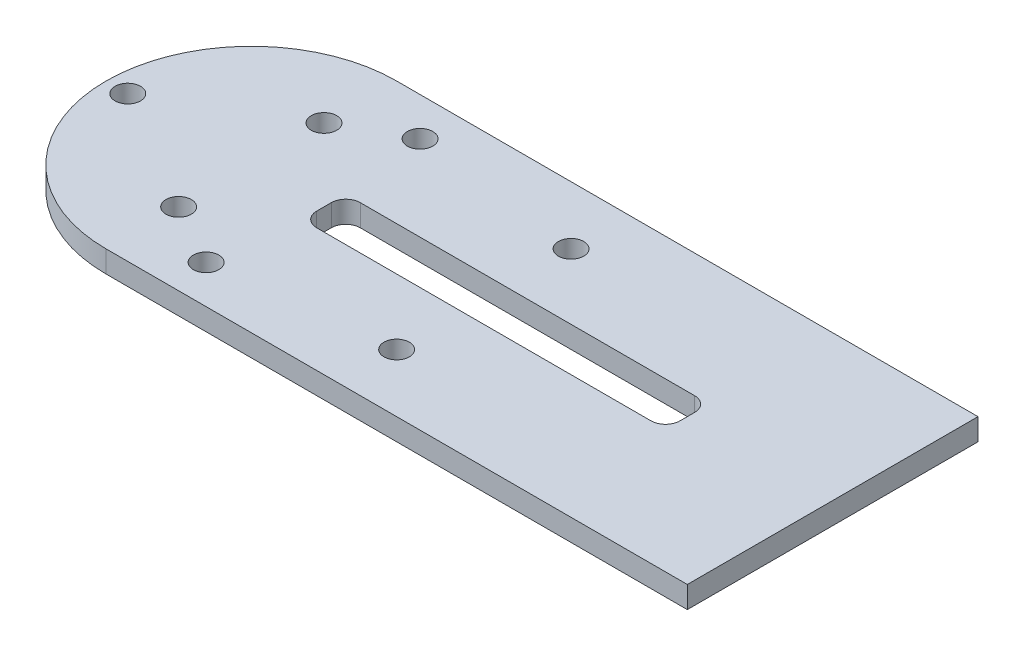
SolidWorks part; units mm, degrees
ref_plane "Front" through (0, 0, 0) normal (0, 0, 1) x (1, 0, 0)
ref_plane "Top" through (0, 0, 0) normal (0, 1, 0) x (1, 0, 0)
ref_plane "Right" through (0, 0, 0) normal (1, 0, 0) x (0, 0, -1)
sketch "Sketch1" plane through (0, 0, 0) normal (0, 1, 0) x (1, 0, 0)
  line L1 (50, -20) -> (-30, -20)
  line L2 (50, -20) -> (50, 20)
  line L3 (50, 20) -> (-30, 20)
  line L5 (50, -20) -> (0, 0) construction
  line L6 (50, 20) -> (0, 0) construction
  arc A0 (-30, 20) -> (-30, -20) centre (-30, 0) ccw
  point P0 (0, 0)
  dimension "D3" = 40
extrude "Boss-Extrude1" add sketch "Sketch1" along normal blind 3
sketch "Sketch2" plane through (0, 3, 0) normal (0, 1, 0) x (1, 0, 0)
  line L0 (-50, 0) -> (50, 0) construction
  line L2 (50, -20) -> (50, 20) construction
  circle A0 centre (-30, 0) radius 12.5 construction
  dimension "D1" = 25
  dimension "D2" = 20
  dimension "D3" = 20
sketch "Sketch3" plane through (0, 3, 0) normal (0, 1, 0) x (1, 0, 0)
  line L0 (-50, 0) -> (50, 0) construction
  circle A0 centre (-30, 10) radius 1.75
  circle A1 centre (-30, -10) radius 1.75
  dimension "D1" = 3.5
  dimension "D2" = 3.5
  dimension "D3" = 10
  dimension "D4" = 10
  dimension "D5" = 20
  dimension "D6" = 20
extrude "Cut-Extrude1" cut sketch "Sketch3" against normal through all
sketch "Sketch4" plane through (0, 0, 0) normal (0, -1, 0) x (1, 0, 0)
  line L0 (-50, 0) -> (50, 0) construction
  line L1 (30, -3) -> (-20, -3)
  line L2 (30, -3) -> (30, 3)
  line L3 (30, 3) -> (-20, 3)
  line L4 (-20, -3) -> (-20, 3)
  line L5 (30, -3) -> (-20, 3) construction
  line L6 (30, 3) -> (-20, -3) construction
  line L7 (-20, -7.5) -> (-20, 7.5) construction
  point P0 (5, 0)
  dimension "D1" = 50
  dimension "D2" = 6
extrude "Cut-Extrude2" cut sketch "Sketch4" against normal up to next
fillet "Fillet1" radius 2 4 edges at (-20, 1.5, -3) (-20, 1.5, 3) (30, 1.5, -3) (30, 1.5, 3)
sketch "Sketch5" plane through (0, 0, 0) normal (0, -1, 0) x (1, 0, 0)
  circle A0 centre (-21.5, -14.7224) radius 1.75
  circle A1 centre (-21.5, 14.7224) radius 1.75
  circle A2 centre (-47, 0) radius 1.75
extrude "Cut-Extrude3" cut sketch "Sketch5" against normal up to next
sketch "Sketch6" plane through (0, 3, 0) normal (0, 1, 0) x (-1, 0, 0)
  line L0 (-10, -20) -> (-10, 20) construction
  line L1 (-50, -20) -> (30, -20) construction
  line L2 (30, 20) -> (-50, 20) construction
  line L3 (-50, 20) -> (-50, -20) construction
  dimension "D1" = 40
sketch "Sketch7" plane through (0, 0, 0) normal (0, -1, 0) x (1, 0, 0)
  line L0 (10, -20) -> (10, 20) construction
  line L1 (50, -20) -> (-30, -20) construction
  line L2 (-30, 20) -> (50, 20) construction
  circle A0 centre (2, 12) radius 1.75
  circle A1 centre (2, -12) radius 1.75
  dimension "D1" = 3.5
  dimension "D2" = 3.5
  dimension "D3" = 8
  dimension "D4" = 8
  dimension "D5" = 8
  dimension "D6" = 8
extrude "Cut-Extrude4" cut sketch "Sketch7" against normal up to next
